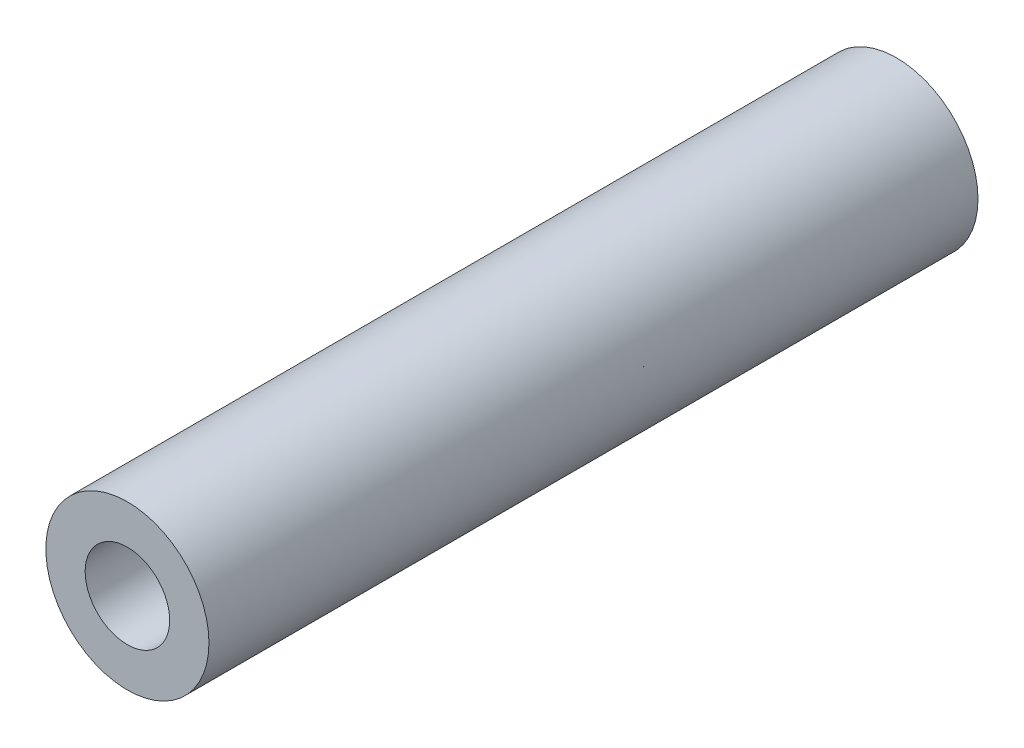
SolidWorks part; units mm, degrees
material "Plain Carbon Steel"
ref_plane "Front Plane" through (0, 0, 0) normal (0, 0, 1) x (1, 0, 0)
ref_plane "Top Plane" through (0, 0, 0) normal (0, 1, 0) x (1, 0, 0)
ref_plane "Right Plane" through (0, 0, 0) normal (1, 0, 0) x (0, 0, -1)
sketch "Sketch1" plane through (0, 0, 0) normal (0, 0, 1) x (1, 0, 0)
  circle A0 centre (0, 0) radius 5
  dimension "D1" = 10
extrude "Boss-Extrude1" add sketch "Sketch1" along normal blind 47.15
hole_wizard "#6 (0.204) Diameter Hole1" positions "Sketch2" profile "Sketch3" hole size "#6" standard "ANSI Inch"
sketch "Sketch2" plane through (0, 0, 0) normal (0, 0, -1) x (-1, 0, 0)
  point P0 (0, 0)
sketch "Sketch3" plane through (0, 0, 0) normal (1, 0, 0) x (0, 1, 0)
  line L0 (0, 0) -> (0, 31.5567)
  line L1 (0, 31.5567) -> (2.5908, 30)
  line L2 (2.5908, 30) -> (2.5908, 0)
  line L5 (2.5908, 0) -> (0, 0)
  line L10 (0, 31.5567) -> (-2.5908, 30) construction
  line L11 (0, -6.35) -> (0, 107.95) construction
  dimension "Hole Dia." = 5.1816
  dimension "Hole Depth" = 30
  dimension "Drill Angle" = 118
hole_wizard "#6 (0.204) Diameter Hole2" positions "Sketch4" profile "Sketch5" hole size "#6" standard "ANSI Inch"
sketch "Sketch4" plane through (0, 0, 47.15) normal (0, 0, 1) x (1, 0, 0)
  point P0 (0, 0)
sketch "Sketch5" plane through (0, 0, 47.15) normal (1, 0, 0) x (0, -1, 0)
  line L0 (0, 0) -> (0, 31.5567)
  line L1 (0, 31.5567) -> (2.5908, 30)
  line L2 (2.5908, 30) -> (2.5908, 0)
  line L5 (2.5908, 0) -> (0, 0)
  line L10 (0, 31.5567) -> (-2.5908, 30) construction
  line L11 (0, -6.35) -> (0, 107.95) construction
  dimension "Hole Dia." = 5.1816
  dimension "Hole Depth" = 30
  dimension "Drill Angle" = 118
